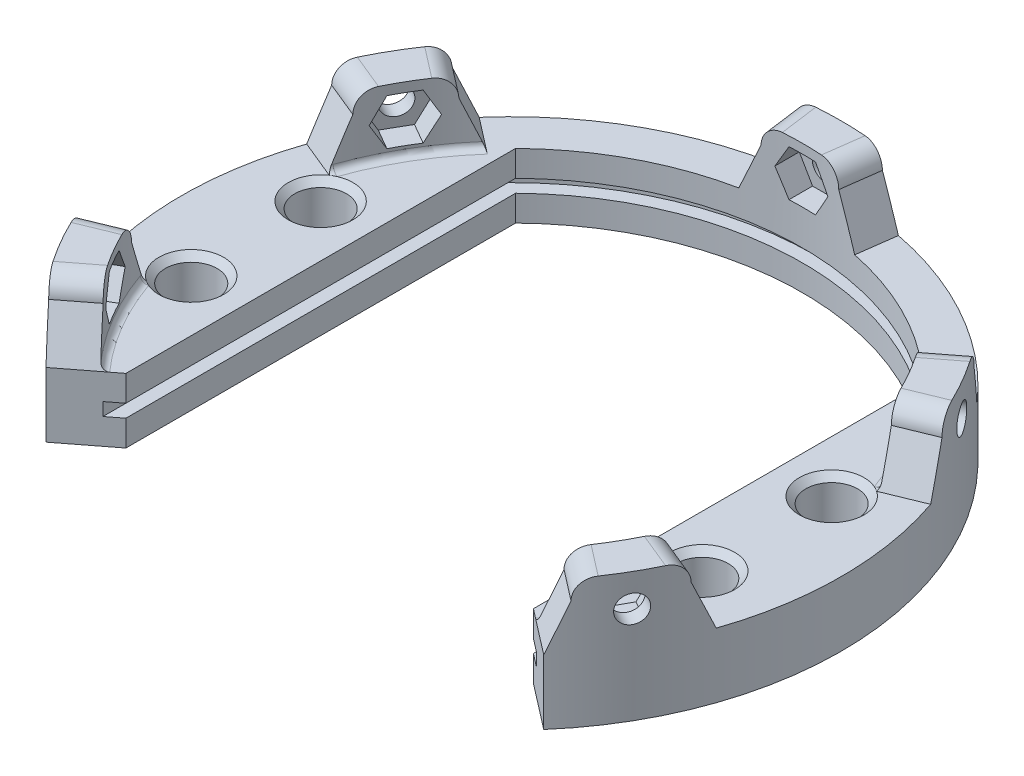
SolidWorks part; units mm, degrees
ref_plane "Спереди" through (0, 0, 0) normal (0, 0, 1) x (1, 0, 0)
ref_plane "Сверху" through (0, 0, 0) normal (0, 1, 0) x (1, 0, 0)
ref_plane "Справа" through (0, 0, 0) normal (1, 0, 0) x (0, 0, -1)
sketch "Эскиз3" plane through (0, 0, 0) normal (0, 1, 0) x (1, 0, 0)
  line L0 (-32.5, 32.5538) -> (-32.5, -32.5538) construction
  line L1 (32.5, -32.5538) -> (32.5, 32.5538) construction
  line L2 (-32.5, 32.5538) -> (-32.5, -32.5538) construction
  line L3 (32.5, -32.5538) -> (32.5, 32.5538) construction
  line L4 (-31.5, 32.1364) -> (-31.5, -32.5538)
  line L5 (31.5, -32.5538) -> (31.5, 32.1364)
  line L6 (-31.5, 32.5538) -> (-31.5, -32.5538) construction
  line L7 (31.5, -32.5538) -> (31.5, 32.5538) construction
  line L8 (31.5, -32.5538) -> (31.5, -40.1092)
  line L9 (-31.5, -32.5538) -> (-31.5, -40.1092)
  line L10 (-1000, 0) -> (49000, 0) construction
  line L11 (0, -1000) -> (0, 49000) construction
  circle A0 centre (0, 0) radius 51
  arc A1 (31.5, 32.1364) -> (-31.5, 32.1364) centre (0, 0) ccw
  arc A2 (32.5, 32.5538) -> (-32.5, 32.5538) centre (0, 0) ccw construction
  arc A3 (32.5, 32.5538) -> (-32.5, 32.5538) centre (0, 0) ccw construction
  arc A4 (31.7935, 31.8461) -> (-31.7935, 31.8461) centre (0, 0) ccw construction
  circle A5 centre (39.5, 10) radius 4
  circle A6 centre (39.5, -10) radius 4
  circle A7 centre (-39.5, -10) radius 4
  circle A8 centre (-39.5, 10) radius 4
  dimension "D1" = 102
  dimension "D3" = 8
  dimension "D4" = 8
  dimension "D5" = 20
  dimension "D2" = 1
extrude "Бобышка-Вытянуть1" add sketch "Эскиз3" along normal mid plane 10 contours A1 L5 L8 A0 L9 L4 A6 A5 A7 A8 region at (-32.8677, 0, 0.2087)
sketch "Эскиз4" plane through (0, 0, 0) normal (0, 1, 0) x (1, 0, 0)
  line L0 (33.5, -32.5538) -> (33.5, 32.9659)
  line L1 (-33.5, 32.9659) -> (-33.5, -32.5538)
  line L2 (32.5, -32.5538) -> (32.5, 32.5538)
  line L3 (-32.5, 32.5538) -> (-32.5, -32.5538)
  line L4 (32.5, -32.5538) -> (32.5, 32.5538) construction
  line L5 (-32.5, 32.5538) -> (-32.5, -32.5538) construction
  line L6 (-33.5, -32.5538) -> (-33.5, -38.4545)
  line L7 (33.5, -32.5538) -> (33.5, -38.4545)
  line L8 (31.5, 32.1364) -> (31.5, -40.1092)
  line L9 (-31.5, -40.1092) -> (-31.5, 32.1364)
  line L10 (31.5, 32.1364) -> (31.5, -40.1092) construction
  line L11 (-31.5, -40.1092) -> (-31.5, 32.1364) construction
  line L12 (-31.5, -40.1092) -> (31.5, -40.1092)
  arc A0 (33.5, 32.9659) -> (-33.5, 32.9659) centre (0, 0) ccw
  arc A1 (33.5, -38.4545) -> (-33.5, -38.4545) centre (0, 0) ccw construction
  arc A2 (-32.5, -32.5538) -> (32.5, -32.5538) centre (0, 0) ccw
  arc A3 (32.5, 32.5538) -> (-32.5, 32.5538) centre (0, 0) ccw
  arc A4 (-32.5, -32.5538) -> (32.5, -32.5538) centre (0, 0) ccw construction
  arc A5 (32.5, 32.5538) -> (-32.5, 32.5538) centre (0, 0) ccw construction
  arc A6 (-33.5, -38.4545) -> (-31.5, -40.1092) centre (0, 0) ccw
  arc A7 (31.5, 32.1364) -> (-31.5, 32.1364) centre (0, 0) ccw
  arc A8 (31.5, -40.1092) -> (-31.5, -40.1092) centre (0, 0) ccw
  arc A9 (31.5, 32.1364) -> (-31.5, 32.1364) centre (0, 0) ccw construction
  arc A10 (31.5, -40.1092) -> (33.5, -38.4545) centre (0, 0) ccw
  dimension "D1" = 0
  dimension "D2" = 1
  dimension "D3" = 0
extrude "Вырез-Вытянуть1" cut sketch "Эскиз4" against normal mid plane 2
sketch "Эскиз10" plane through (0, 5, 0) normal (0, 1, 0) x (1, 0, 0)
  line L0 (0, -1000) -> (0, 49000) construction
  line L1 (-1000, 0) -> (49000, 0) construction
  line L2 (0, 0) -> (44.1673, 25.5) construction
  line L3 (35.6232, 27.4953) -> (40.3729, 31.1613)
  line L4 (41.6232, 17.103) -> (47.1729, 19.3833)
  line L5 (41.6232, -17.103) -> (47.1729, -19.3833)
  line L6 (35.6232, -27.4953) -> (40.3729, -31.1613)
  line L7 (-35.6232, -27.4953) -> (-40.3729, -31.1613)
  line L8 (-41.6232, -17.103) -> (-47.1729, -19.3833)
  line L9 (-41.6232, 17.103) -> (-47.1729, 19.3833)
  line L10 (-35.6232, 27.4953) -> (-40.3729, 31.1613)
  line L11 (-6, 44.5982) -> (-6.8, 50.5446)
  line L12 (6, 44.5982) -> (6.8, 50.5446)
  line L13 (0, 45) -> (0, 0) construction
  arc A0 (31.5, -40.1092) -> (-31.5, -40.1092) centre (0, 0) ccw construction
  arc A1 (6.8, 50.5446) -> (-6.8, 50.5446) centre (0, 0) ccw
  arc A2 (-6, 44.5982) -> (6, 44.5982) centre (0, 0) cw
  arc A5 (47.1729, 19.3833) -> (40.3729, 31.1613) centre (0, 0) ccw
  arc A7 (35.6232, 27.4953) -> (41.6232, 17.103) centre (0, 0) cw
  arc A8 (35.6232, -27.4953) -> (41.6232, -17.103) centre (0, 0) ccw
  arc A9 (47.1729, -19.3833) -> (40.3729, -31.1613) centre (0, 0) cw
  arc A10 (-47.1729, -19.3833) -> (-47.1729, 19.3833) centre (0, 0) cw construction
  arc A11 (-31.5, -40.1092) -> (-51, 0) centre (0, 0) cw construction
  arc A12 (-47.1729, -19.3833) -> (-40.3729, -31.1613) centre (0, 0) ccw
  arc A13 (-35.6232, -27.4953) -> (-41.6232, -17.103) centre (0, 0) cw
  arc A14 (-35.6232, 27.4953) -> (-41.6232, 17.103) centre (0, 0) ccw
  arc A15 (-47.1729, 19.3833) -> (-40.3729, 31.1613) centre (0, 0) cw
  point P33 (0, 0)
  dimension "D1" = 6
  dimension "D2" = 12
  dimension "D3" = 30
  dimension "D4" = 2
extrude "Бобышка-Вытянуть2" add sketch "Эскиз10" along normal blind 10
fillet "Скругление1" radius 3 10 edges at (-44.3981, 15, 18.2431) (-37.9981, 15, 29.3283) (-44.3981, 15, -18.2431) (-37.9981, 15, -29.3283) (37.9981, 15, 29.3283) (44.3981, 15, -18.2431) (44.3981, 15, 18.2431) (37.9981, 15, -29.3283) (6.4, 15, -47.5714) (-6.4, 15, -47.5714)
chamfer "Фаска1" distance 1 angle 45 4 edges at (39.5, 5, 14) (39.5, 5, -6) (-39.5, 5, 14) (-39.5, 5, -6)
ref_plane "Плоскость1" through (0, 0, -44.5982) normal (0, 0, 1) x (1, 0, 0)
sketch "Эскиз11" plane through (0, 0, -44.5982) normal (0, 0, 1) x (1, 0, 0)
  line L0 (0, -1000) -> (0, 49000) construction
  line L1 (3.0134, 15) -> (-3.0134, 15) construction
  line L2 (3.0134, 15) -> (-3.0134, 15)
  line L3 (31.5, 5) -> (6, 5) construction
  circle A0 centre (0, 10) radius 2.1
  dimension "D1" = 4.2
  dimension "D2" = 10
  dimension "D3" = 5
extrude "Вырез-Вытянуть5" cut sketch "Эскиз11" against normal through all contours A0 L0 | L0 A0 region at (-0.8913, 10, -44.5982) region at (0.8913, 10, -44.5982)
sketch "Эскиз12" plane through (0, 0, -44.5982) normal (0, 0, 1) x (1, 0, 0)
  line L0 (0, -1000) -> (0, 49000) construction
  line L2 (4.0992, 10) -> (2.0496, 13.55)
  line L3 (2.0496, 13.55) -> (-2.0496, 13.55)
  line L4 (-2.0496, 13.55) -> (-4.0992, 10)
  line L5 (-4.0992, 10) -> (-2.0496, 6.45)
  line L6 (-2.0496, 6.45) -> (2.0496, 6.45)
  line L7 (2.0496, 6.45) -> (4.0992, 10)
  circle A0 centre (0, 10) radius 2.1 construction
  circle A1 centre (0, 10) radius 2.1
  circle A2 centre (0, 10) radius 3.55 construction
  dimension "D1" = 7.1
extrude "Вырез-Вытянуть6" cut sketch "Эскиз12" against normal blind 4
chamfer "Фаска3" distance 3 distance2 7 10 edges at (-44.3981, 5, -18.2431) (-37.9981, 5, 29.3283) (-44.3981, 5, 18.2431) (44.3981, 5, 18.2431) (37.9981, 5, 29.3283) (44.3981, 5, -18.2431) (37.9981, 5, -29.3283) (6.4, 5, -47.5714) (-6.4, 5, -47.5714) (-37.9981, 5, -29.3283) first distance on face at (-39.5, 5, 15) first distance on face at (39.5, 5, 15)
fillet "Скругление2" radius 1 4 edges at (-38.9711, 5, 22.5) (-38.9711, 5, -22.5) (38.9711, 5, 22.5) (38.9711, 5, -22.5)
chamfer "Фаска4" distance 1 angle 45 4 edges at (39.5, -5, -6) (39.5, -5, 14) (-39.5, -5, -6) (-39.5, -5, 14)
sketch "Эскиз13" plane through (0, 0, 0) normal (0, 0, 1) x (1, 0, 0)
  line L0 (0, -1000) -> (0, 49000) construction
pattern_circular "Круговой массив1" count 6 over 360 about axis through (0, -1000, 0) along (0, 1, 0) skipping 3 of "Вырез-Вытянуть6", "Вырез-Вытянуть5"
sketch "Эскиз14" plane through (0, 5, 0) normal (0, 1, 0) x (1, 0, 0)
  line L0 (31.5, -40.1092) -> (31.5, 32.1364) construction
  line L1 (-31.5, 32.1364) -> (-31.5, -40.1092) construction
  line L2 (38.47, -33.4822) -> (32.9175, -29.1966) construction
  line L3 (-32.9175, -29.1966) -> (-38.47, -33.4822) construction
  line L4 (31.5, -40.1092) -> (31.5, -28.1025)
  line L5 (-31.5, -28.1025) -> (-31.5, -40.1092)
  line L6 (38.47, -33.4822) -> (32.9175, -29.1966)
  line L7 (-32.9175, -29.1966) -> (-38.47, -33.4822)
  line L8 (-32.9175, -29.1966) -> (-31.5, -28.1025)
  line L9 (32.9175, -29.1966) -> (31.5, -28.1025)
  arc A0 (31.5, -40.1092) -> (38.47, -33.4822) centre (0, 0) ccw construction
  arc A1 (-38.47, -33.4822) -> (-31.5, -40.1092) centre (0, 0) ccw construction
  arc A2 (31.5, -40.1092) -> (38.47, -33.4822) centre (0, 0) ccw
  arc A3 (-38.47, -33.4822) -> (-31.5, -40.1092) centre (0, 0) ccw
extrude "Вырез-Вытянуть7" cut sketch "Эскиз14" against normal through all
sketch "Эскиз17" plane through (0, -5, 0) normal (0, -1, 0) x (1, 0, 0)
  line L0 (0, -1000) -> (0, 49000) construction
  line L1 (-1000, 0) -> (49000, 0) construction
  circle A0 centre (37, 25) radius 1.5
  circle A1 centre (-37, 25) radius 1.5
  dimension "D1" = 3
  dimension "D2" = 25
  dimension "D3" = 37
extrude "Вырез-Вытянуть8" cut sketch "Эскиз17" against normal blind 5
equation "\"D3@Эскиз11\"=\"D2@Эскиз11\"/2"
